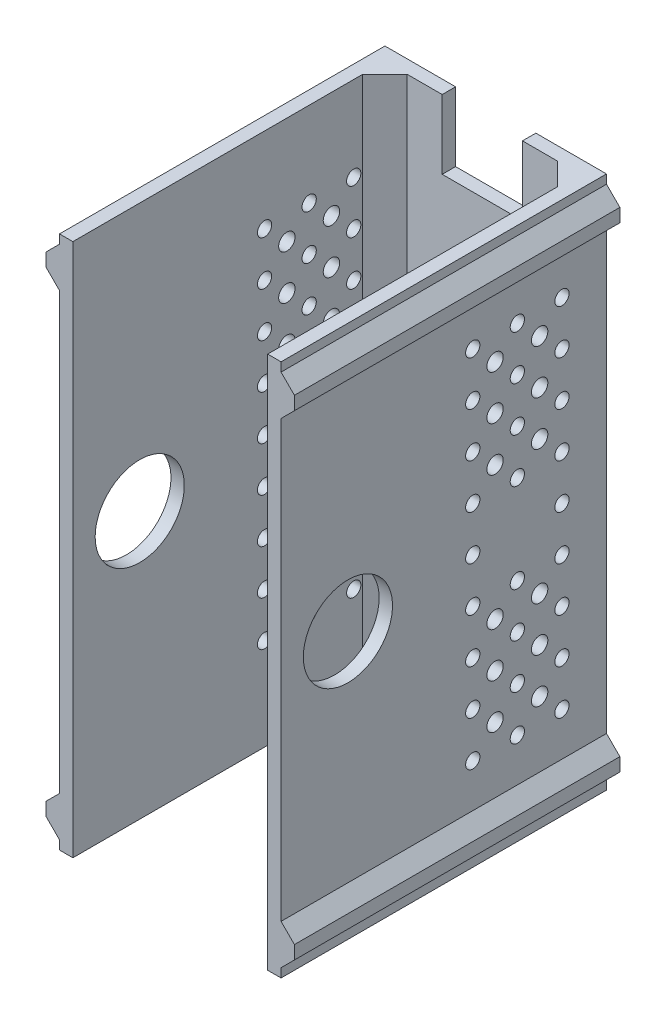
SolidWorks part; units mm, degrees
ref_plane "Front Plane" through (0, 0, 0) normal (0, 0, 1) x (1, 0, 0)
ref_plane "Top Plane" through (0, 0, 0) normal (0, 1, 0) x (1, 0, 0)
ref_plane "Right Plane" through (0, 0, 0) normal (1, 0, 0) x (0, 0, -1)
sketch "Sketch1" plane through (0, 0, 0) normal (0, 0, 1) x (1, 0, 0)
  line L0 (9, 0) -> (-9, 0)
  line L1 (-9, 0) -> (-9, -15.5)
  line L2 (-9, -15.5) -> (-24.85, -15.5)
  line L3 (-24.85, -15.5) -> (-24.85, -10.5)
  line L4 (-24.85, 44.35) -> (24.85, 44.35) construction
  line L5 (0, 88.7) -> (0, 0) construction
  line L6 (-24.85, -10.5) -> (-27.85, -10.5)
  line L7 (-27.85, -10.5) -> (-27.85, -7.5)
  line L8 (-27.85, -7.5) -> (-24.85, -7.5)
  line L9 (-24.85, -7.5) -> (-24.85, 36.35)
  line L10 (-24.85, 36.35) -> (-24.85, 41.85)
  line L11 (24.85, 41.85) -> (24.85, 46.85)
  line L12 (24.85, 36.35) -> (24.85, 41.85)
  line L13 (-24.85, 41.85) -> (-24.85, 46.85)
  line L14 (24.85, -7.5) -> (24.85, 36.35)
  line L15 (27.85, -7.5) -> (24.85, -7.5)
  line L16 (27.85, -10.5) -> (27.85, -7.5)
  line L17 (24.85, -10.5) -> (27.85, -10.5)
  line L18 (24.85, -15.5) -> (24.85, -10.5)
  line L19 (9, -15.5) -> (24.85, -15.5)
  line L20 (9, 0) -> (9, -15.5)
  line L21 (9, 88.7) -> (9, 104.2)
  line L22 (9, 104.2) -> (24.85, 104.2)
  line L23 (24.85, 104.2) -> (24.85, 99.2)
  line L24 (24.85, 99.2) -> (27.85, 99.2)
  line L25 (27.85, 99.2) -> (27.85, 96.2)
  line L26 (27.85, 96.2) -> (24.85, 96.2)
  line L27 (24.85, 96.2) -> (24.85, 52.35)
  line L28 (24.85, 52.35) -> (24.85, 46.85)
  line L29 (-24.85, 52.35) -> (-24.85, 46.85)
  line L30 (-24.85, 96.2) -> (-24.85, 52.35)
  line L31 (-27.85, 96.2) -> (-24.85, 96.2)
  line L32 (-27.85, 99.2) -> (-27.85, 96.2)
  line L33 (-24.85, 99.2) -> (-27.85, 99.2)
  line L34 (-24.85, 104.2) -> (-24.85, 99.2)
  line L35 (-9, 104.2) -> (-24.85, 104.2)
  line L36 (-9, 88.7) -> (-9, 104.2)
  line L37 (9, 88.7) -> (-9, 88.7)
  point P24 (0, 44.35)
  dimension "D1" = 9
  dimension "D2" = 15.5
  dimension "D3" = 15.85
  dimension "D4" = 59.85
  dimension "D5" = 3
  dimension "D6" = 5
extrude "Boss-Extrude1" add sketch "Sketch1" along normal blind 3
sketch "Sketch2" plane through (0, 0, 3) normal (0, 0, 1) x (1, 0, 0)
  line L0 (-24.85, 104.2) -> (-21.85, 104.2)
  line L1 (-9, 104.2) -> (-24.85, 104.2) construction
  line L2 (-24.85, 104.2) -> (-24.85, 99.2)
  line L3 (-24.85, 99.2) -> (-27.85, 99.2)
  line L4 (-27.85, 99.2) -> (-27.85, 96.2)
  line L5 (-27.85, 96.2) -> (-24.85, 96.2)
  line L6 (-24.85, 96.2) -> (-24.85, -7.5)
  line L7 (-24.85, -7.5) -> (-27.85, -7.5)
  line L8 (-27.85, -7.5) -> (-27.85, -10.5)
  line L9 (-27.85, -10.5) -> (-24.85, -10.5)
  line L10 (-24.85, -10.5) -> (-24.85, -15.5)
  line L11 (-24.85, -15.5) -> (-21.85, -15.5)
  line L12 (-21.85, 104.2) -> (-21.85, -15.5)
  line L13 (0, 88.7) -> (0, 0) construction
  line L14 (9, 88.7) -> (-9, 88.7) construction
  line L15 (21.85, 104.2) -> (21.85, -15.5)
  line L16 (24.85, -15.5) -> (21.85, -15.5)
  line L17 (24.85, -10.5) -> (24.85, -15.5)
  line L18 (27.85, -10.5) -> (24.85, -10.5)
  line L19 (27.85, -7.5) -> (27.85, -10.5)
  line L20 (24.85, -7.5) -> (27.85, -7.5)
  line L21 (24.85, 96.2) -> (24.85, -7.5)
  line L22 (27.85, 96.2) -> (24.85, 96.2)
  line L23 (27.85, 99.2) -> (27.85, 96.2)
  line L24 (24.85, 99.2) -> (27.85, 99.2)
  line L25 (24.85, 104.2) -> (24.85, 99.2)
  line L26 (24.85, 104.2) -> (21.85, 104.2)
  dimension "D1" = 3
extrude "Boss-Extrude2" add sketch "Sketch2" along normal blind 70
sketch "Sketch3" plane through (0, 0, 0) normal (0, 0, -1) x (-1, 0, 0)
  line L0 (0, 88.7) -> (0, 0) construction
  line L1 (-9, 88.7) -> (9, 88.7) construction
  line L2 (0, 44.35) -> (9, 44.35) construction
  line L3 (0, 70.85) -> (0, 17.85) construction
  circle A0 centre (9, 44.35) radius 1.65
  circle A1 centre (-4.5, 36.5558) radius 1.65
  circle A2 centre (-4.5, 52.1442) radius 1.65
  circle A3 centre (0, 44.35) radius 2.75
  circle A4 centre (0, 70.85) radius 3.5
  circle A5 centre (0, 17.85) radius 3.5
  point P14 (0, 44.35)
  point P16 (0, 44.35)
  dimension "D2" = 3.3
  dimension "D4" = 5.5
  dimension "D6" = 7
  dimension "D1" = 9
  dimension "D5" = 53
  dimension "D3" = 3
extrude "Cut-Extrude1" cut sketch "Sketch3" against normal up to surface (3 mm away) up to face at (0, 44.35, 3)
chamfer "Chamfer1" distance 5 angle 45 2 edges at (21.85, 44.35, 3) (-21.85, 44.35, 3)
chamfer "Chamfer2" distance 3 angle 45 8 edges at (24.85, 99.2, 36.5) (24.85, 96.2, 36.5) (24.85, -10.5, 36.5) (24.85, -7.5, 36.5) (-24.85, -7.5, 36.5) (-24.85, -10.5, 36.5) (-24.85, 99.2, 36.5) (-24.85, 96.2, 36.5)
sketch "Sketch4" plane through (-24.85, 0, 0) normal (-1, 0, 0) x (0, 0, 1)
  line L0 (73, 93.2) -> (73, -4.5) construction
  line L1 (73, 44.35) -> (58, 44.35) construction
  line L2 (10, 85.2) -> (20, 75.2) construction
  line L3 (0, 93.2) -> (10, 93.2) construction
  line L4 (0, 93.2) -> (0, 85.2) construction
  line L5 (0, 85.2) -> (10, 85.2) construction
  line L6 (10, 93.2) -> (10, 85.2) construction
  line L7 (0, 93.2) -> (10, 85.2) construction
  line L8 (0, 85.2) -> (10, 93.2) construction
  circle A0 centre (58, 44.35) radius 10
  circle A1 centre (10, 85.2) radius 1.6
  circle A2 centre (20, 85.2) radius 1.6
  circle A3 centre (30, 85.2) radius 1.6
  circle A4 centre (20, 75.2) radius 1.6
  circle A5 centre (30, 75.2) radius 1.6
  circle A6 centre (20, 65.2) radius 1.6
  circle A7 centre (30, 65.2) radius 1.6
  circle A8 centre (20, 55.2) radius 1.6
  circle A9 centre (30, 55.2) radius 1.6
  circle A10 centre (20, 45.2) radius 1.6 construction
  circle A11 centre (30, 45.2) radius 1.6
  circle A12 centre (20, 35.2) radius 1.6
  circle A13 centre (30, 35.2) radius 1.6
  circle A14 centre (20, 25.2) radius 1.6
  circle A15 centre (30, 25.2) radius 1.6
  circle A16 centre (20, 15.2) radius 1.6
  circle A17 centre (30, 15.2) radius 1.6
  circle A18 centre (20, 5.2) radius 1.6
  circle A19 centre (30, 5.2) radius 1.6
  circle A20 centre (10, 75.2) radius 1.6
  circle A21 centre (10, 65.2) radius 1.6
  circle A22 centre (10, 55.2) radius 1.6
  circle A23 centre (10, 45.2) radius 1.6
  circle A24 centre (10, 35.2) radius 1.6
  circle A25 centre (10, 25.2) radius 1.6
  circle A26 centre (10, 15.2) radius 1.6
  circle A27 centre (10, 5.2) radius 1.6
  circle A28 centre (15, 80.2) radius 1.8421
  circle A29 centre (25, 80.2) radius 1.8421
  circle A30 centre (25, 70.2) radius 1.8421
  circle A31 centre (25, 60.2) radius 1.8421
  circle A32 centre (25, 50.2) radius 1.8421 construction
  circle A33 centre (25, 40.2) radius 1.8421 construction
  circle A34 centre (25, 30.2) radius 1.8421
  circle A35 centre (25, 20.2) radius 1.8421
  circle A36 centre (25, 10.2) radius 1.8421
  circle A37 centre (15, 70.2) radius 1.8421
  circle A38 centre (15, 60.2) radius 1.8421
  circle A39 centre (15, 50.2) radius 1.8421 construction
  circle A40 centre (15, 40.2) radius 1.8421 construction
  circle A41 centre (15, 30.2) radius 1.8421
  circle A42 centre (15, 20.2) radius 1.8421
  circle A43 centre (15, 10.2) radius 1.8421
  point P11 (5, 89.2)
  point P68 (0, 0)
  dimension "D2" = 20
  dimension "D4" = 3.2
  dimension "D8" = 3.6841
  dimension "D1" = 15
  dimension "D3" = 10
  dimension "D7" = 8
  dimension "D5" = 3
  dimension "D6" = 9
  dimension "D9" = 2
  dimension "D10" = 8
extrude "Cut-Extrude2" cut sketch "Sketch4" against normal through all
